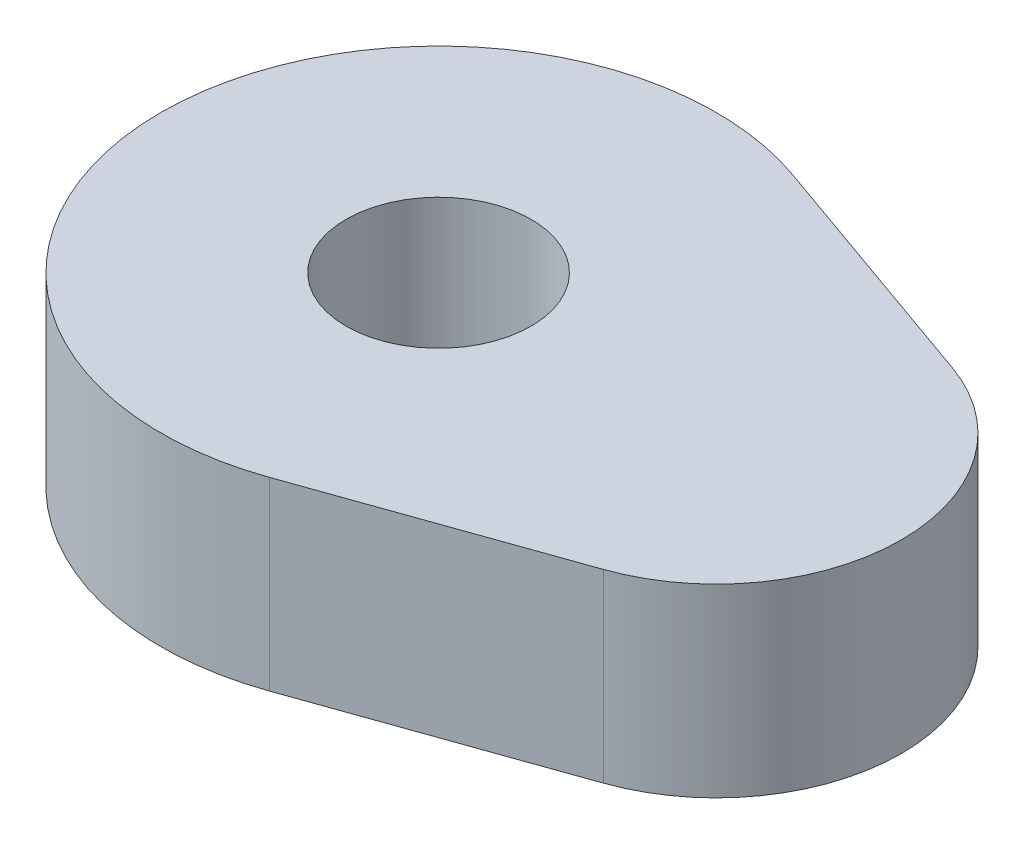
SolidWorks part; units mm, degrees
ref_plane "前视基准面" through (0, 0, 0) normal (0, 0, 1) x (1, 0, 0)
ref_plane "上视基准面" through (0, 0, 0) normal (0, 1, 0) x (1, 0, 0)
ref_plane "右视基准面" through (0, 0, 0) normal (1, 0, 0) x (0, 0, -1)
other "Configuration Table"
sketch "草图1" plane through (0, 0, 0) normal (0, 1, 0) x (1, 0, 0)
  line L0 (5, 14.1421) -> (18.3333, 9.4281)
  line L1 (18.3333, -9.4281) -> (5, -14.1421)
  line L2 (0, 0) -> (15, 0) construction
  arc A0 (5, 14.1421) -> (5, -14.1421) centre (0, 0) ccw
  arc A1 (18.3333, 9.4281) -> (18.3333, -9.4281) centre (15, 0) cw
  dimension "D1" = 15
  dimension "D2" = 10
  dimension "D3" = 15
extrude "凸台-拉伸1" add sketch "草图1" along normal blind 10
sketch "草图2" plane through (0, 10, 0) normal (0, 1, 0) x (1, 0, 0)
  circle A0 centre (0, 0) radius 5
  dimension "D1" = 10
extrude "切除-拉伸1" cut sketch "草图2" against normal through all both and the other way through all
